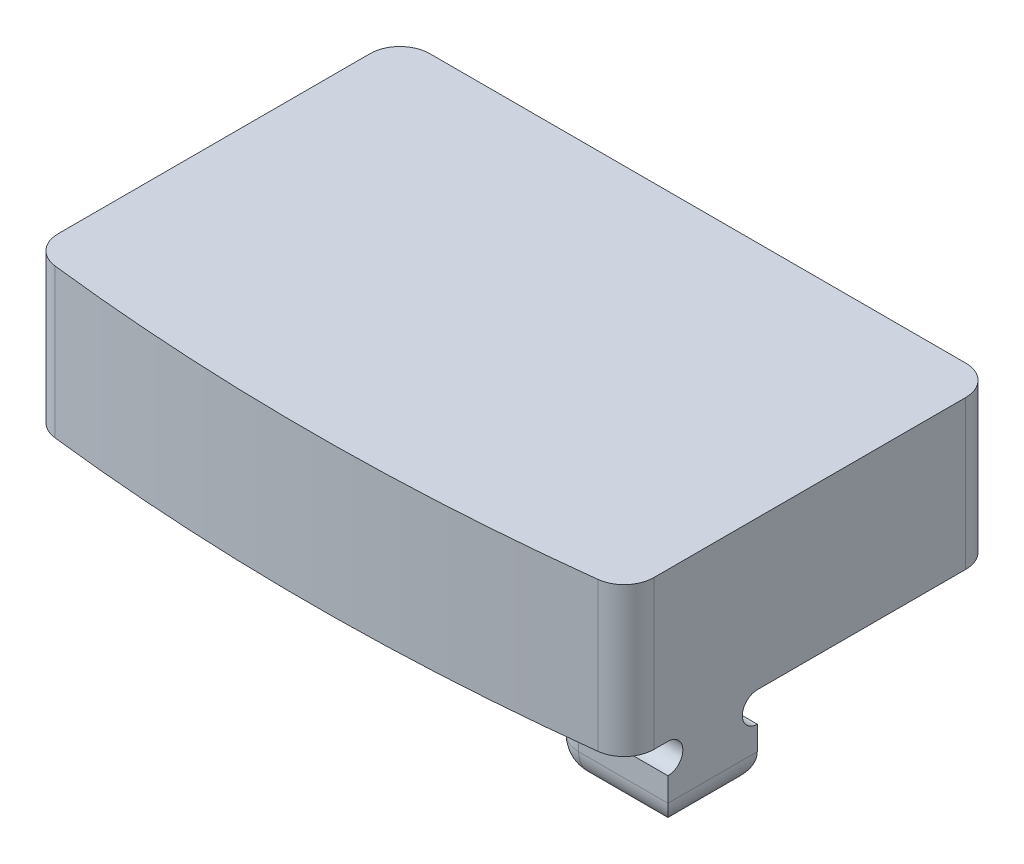
SolidWorks part; units mm, degrees
material "6061 Alloy"
ref_plane "Front Plane" through (0, 0, 0) normal (0, 0, 1) x (1, 0, 0)
ref_plane "Top Plane" through (0, 0, 0) normal (0, 1, 0) x (1, 0, 0)
ref_plane "Right Plane" through (0, 0, 0) normal (1, 0, 0) x (0, 0, -1)
sketch "Sketch1" plane through (0, 0, 0) normal (0, 1, 0) x (1, 0, 0)
  line L0 (10.5, 0) -> (10.5, 78) construction
  line L2 (0.5, 0.6437) -> (0.5, 13)
  line L3 (0.5, 13) -> (20.5, 13)
  line L4 (20.5, 0.6437) -> (20.5, 13)
  line L5 (10.5, 78) -> (10.5, 4) construction
  circle A0 centre (5.5, 9) radius 1.5
  circle A1 centre (15.5, 9) radius 1.5
  arc A4 (0.5, 0.6437) -> (20.5, 0.6437) centre (10.5, 78) ccw
  dimension "D3" = 3
  dimension "D4" = 3
  dimension "D1" = 20
  dimension "D2" = 10
  dimension "D5" = 5
  dimension "D6" = 4
  dimension "D7" = 5
  dimension "D8" = 9
  dimension "D9" = 13
  dimension "D10" = 74
extrude "Boss-Extrude1" add sketch "Sketch1" along normal blind 5 contours L3 L4 A4 L2
fillet "Fillet1" radius 1 4 edges at (20.5, 2.5, -13) (0.5, 2.5, -13) (20.5, 2.5, -0.6437) (0.5, 2.5, -0.6437)
sketch "Sketch3" plane through (0, 0, 0) normal (0, -1, 0) x (1, 0, 0)
  line L0 (1.5, -13) -> (19.5, -13) construction
  line L1 (20.5, -1.5278) -> (20.5, -12) construction
  line L3 (0.5, -1.5278) -> (0.5, -12) construction
  circle A0 centre (5.5, -9) radius 0.7835
  circle A1 centre (15.5, -9) radius 0.7835
  point P4 (0, 0)
  point P9 (5.0779, -13)
  dimension "D4" = 1.567
  dimension "D2" = 4
  dimension "D3" = 5
  dimension "D1" = 5
extrude "Cut-Extrude1" cut sketch "Sketch3" against normal blind 4 contours A1 | A0 region at (5.5, 0, -9) region at (15.5, 0, -9)
sketch "Sketch5" plane through (20.5, 0, 0) normal (1, 0, 0) x (0, 0, -1)
  line L0 (1.5278, 0) -> (12, 0) construction
  line L1 (2, 0) -> (5, 0)
  line L2 (2, -1) -> (2, -2.8)
  line L3 (2, -2.8) -> (5, -2.8)
  line L4 (5, -1) -> (5, -2.8)
  line L5 (13, 5) -> (13, 0) construction
  arc A0 (2, -1) -> (2, 0) centre (2, -0.5) ccw
  arc A1 (5, 0) -> (5, -1) centre (5, -0.5) ccw
  point P12 (0, 0)
  dimension "D4" = 1
  dimension "D1" = 8
  dimension "D2" = 3
  dimension "D3" = 2.8
extrude "Boss-Extrude3" add sketch "Sketch5" against normal blind 4 contours L2 L3 L4 A1 L1 A0
fillet "Fillet2" radius 1 6 edges at (18.5, -2.8, -5) (16.5, -2.8, -3.5) (18.5, -2.8, -2) (20.5, -2.8, -3.5) (16.5, -1.9, -2) (16.5, -1.9, -5)
